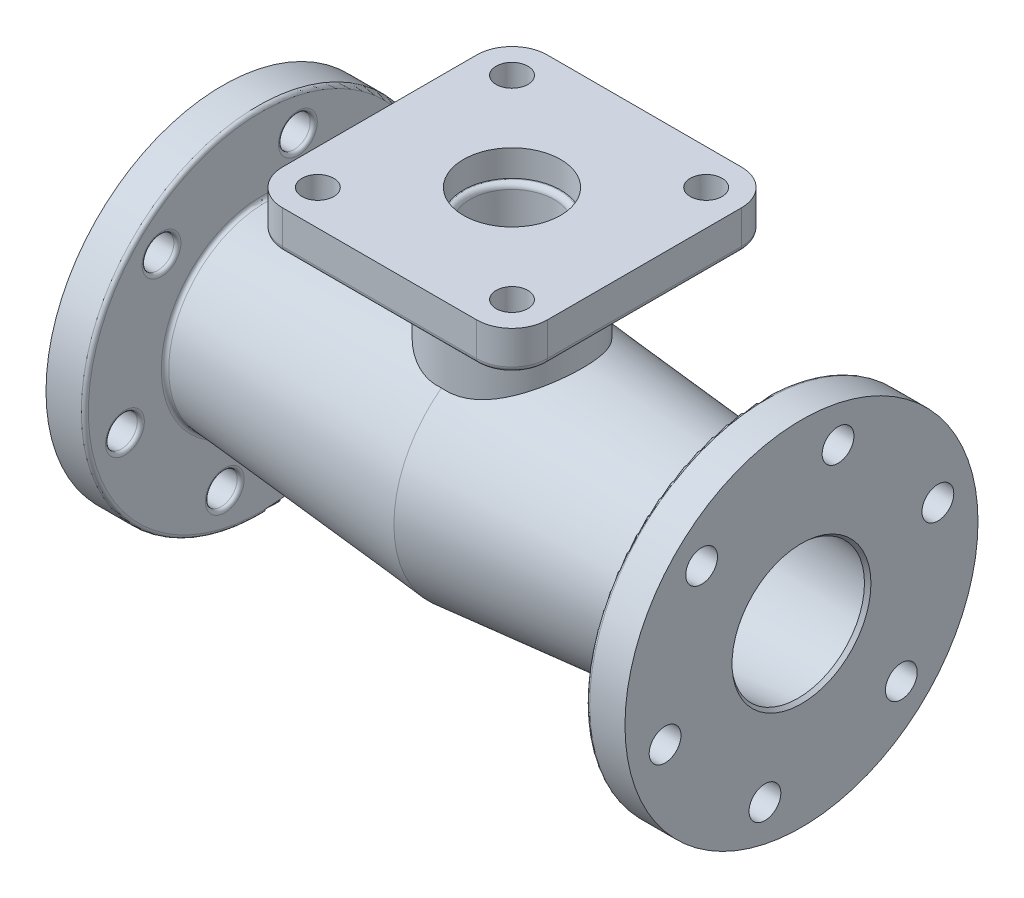
SolidWorks part; units mm, degrees
ref_plane "Front Plane" through (0, 0, 0) normal (0, 0, 1) x (1, 0, 0)
ref_plane "Top Plane" through (0, 0, 0) normal (0, 1, 0) x (1, 0, 0)
ref_plane "Right Plane" through (0, 0, 0) normal (1, 0, 0) x (0, 0, -1)
sketch "Sketch1" plane through (0, 0, 0) normal (0, 0, 1) x (1, 0, 0)
  line L0 (0, 0) -> (0, 213576.62) construction
  line L1 (0, 0) -> (213576.62, 0) construction
  line L2 (-164, -37.5) -> (-164, -100)
  line L3 (-164, -100) -> (-142, -100)
  line L4 (-142, -100) -> (-142, -54.482)
  line L5 (-142, -54.482) -> (0, -66.9054)
  line L6 (-164, -37.5) -> (0, -51.8481)
  line L7 (164, -37.5) -> (0, -51.8481)
  line L8 (142, -54.482) -> (0, -66.9054)
  line L9 (142, -100) -> (142, -54.482)
  line L10 (164, -100) -> (142, -100)
  line L11 (164, -37.5) -> (164, -100)
  point P15 (-82, -44.6741)
  dimension "D1" = 284
  dimension "D2" = 328
  dimension "D3" = 200
  dimension "D4" = 75
  dimension "D5" = 5
  dimension "D6" = 15
revolve "Revolve1" add sketch "Sketch1" angle 360 about L1
hole_wizard "Ø5.0mm Dowel Hole1" positions "Sketch4" profile "Sketch5" hole size "Ø5.0" standard "ANSI Metric" end condition up to next
sketch "Sketch4" plane through (164, 0, 0) normal (1, 0, 0) x (0, 0, -1)
  line L0 (0, 0) -> (0, 50000) construction
  line L1 (0, 0) -> (-50000, 0) construction
  line L2 (0, 0) -> (-48166.4359, -12906.1576) construction
  circle A0 centre (0, 0) radius 80 construction
  point P0 (-77.2741, -20.7055)
  dimension "D1" = 160
  dimension "D2" = 15
sketch "Sketch5" plane through (164, -20.7055, 77.2741) normal (0, 1, 0) x (0, 0, -1)
  line L0 (0, 0) -> (0, 22)
  line L1 (0, 22) -> (9, 22)
  line L2 (9, 22) -> (9, 0)
  line L5 (9, 0) -> (0, 0)
  line L11 (0, -6.35) -> (0, 107.95) construction
  dimension "Thru Hole Dia." = 18
  dimension "Thru Hole Depth" = 22
pattern_circular "CirPattern1" count 6 over 360 about axis through (164, 0, 0) along (-1, 0, 0) of "Ø5.0mm Dowel Hole1"
mirror "Mirror1" about plane through (0, 0, 0) normal (1, 0, 0) of "Ø5.0mm Dowel Hole1", "CirPattern1"
ref_plane "Plane1" through (0, 132, 0) normal (0, 1, 0) x (1, 0, 0)
sketch "Sketch7" plane through (0, 132, 0) normal (0, 1, 0) x (1, 0, 0)
  line L1 (-55, -75) -> (55, -75)
  line L2 (-75, -55) -> (-75, 55)
  line L3 (-55, 75) -> (55, 75)
  line L4 (75, -55) -> (75, 55)
  line L5 (-75, -75) -> (75, 75) construction
  line L6 (-75, 75) -> (75, -75) construction
  arc A0 (55, -75) -> (75, -55) centre (55, -55) ccw
  arc A1 (-75, 55) -> (-55, 75) centre (-55, 55) cw
  arc A2 (-55, -75) -> (-75, -55) centre (-55, -55) cw
  arc A3 (55, 75) -> (75, 55) centre (55, 55) cw
  circle A4 centre (0, 0) radius 40
  circle A5 centre (-55, 55) radius 9
  circle A6 centre (55, 55) radius 9
  circle A7 centre (55, -55) radius 9
  circle A8 centre (-55, -55) radius 9
  point P0 (0, 0)
  dimension "D3" = 20
  dimension "D4" = 80
  dimension "D5" = 18
  dimension "D6" = 18
  dimension "D7" = 18
  dimension "D8" = 18
  dimension "D1" = 150
  dimension "D2" = 150
extrude "Boss-Extrude1" add sketch "Sketch7" against normal blind 22 separate body
extrude "Boss-Extrude2" add sketch "Sketch7<2>" against normal up to body contours A4
sketch "Sketch7<2>" plane through (0, 132, 0) normal (0, 1, 0) x (1, 0, 0) same geometry as "Sketch7"
sketch "Sketch8" plane through (0, 0, 0) normal (0, 0, 1) x (1, 0, 0)
  line L0 (0, 0) -> (0, 50000) construction
  line L2 (0, 132) -> (27.5, 132)
  line L3 (27.5, 132) -> (27.5, 117)
  line L4 (27.5, 117) -> (24, 117)
  line L5 (24, 117) -> (21.9578, 0)
  line L6 (21.9578, 0) -> (0, 0)
  line L7 (0, 0) -> (0, 132)
  line L8 (-55, 132) -> (55, 132) construction
  dimension "D1" = 15
  dimension "D2" = 55
  dimension "D3" = 48
  dimension "D4" = 1
revolve "Cut-Revolve1" cut sketch "Sketch8" angle 360 about L0
fillet "Fillet1" radius 3 1 edges at (24, 117, 0)
fillet "Fillet2" radius 3 8 edges at (-69.1421, 110, 69.1421) (-75, 110, 0) (-69.1421, 110, -69.1421) (0, 110, -75) (69.1421, 110, -69.1421) (75, 110, 0) (69.1421, 110, 69.1421) (0, 110, 75)
fillet "Fillet3" radius 2 16 edges at (142, 0, 54.482) (142, 0, 100) (142, -20.7055, 86.2741) (142, 56.5685, 65.5685) (142, 77.2741, -11.7055) (142, 20.7055, -68.2741) (142, -56.5685, -47.5685) (142, -77.2741, 29.7055) (-142, 0, 100) (-142, 0, 54.482) (-142, -20.7055, 68.2741) (-142, 56.5685, 47.5685) (-142, 77.2741, -29.7055) (-142, 20.7055, -86.2741) (-142, -56.5685, -65.5685) (-142, -77.2741, 11.7055)
chamfer "Chamfer1" distance 2 angle 45 2 edges at (-164, 0, 37.5) (164, 0, 37.5) first distance on face at (-164, -77.2741, 29.7055) first distance on face at (11.3886, -1.0079, -0.7573)
